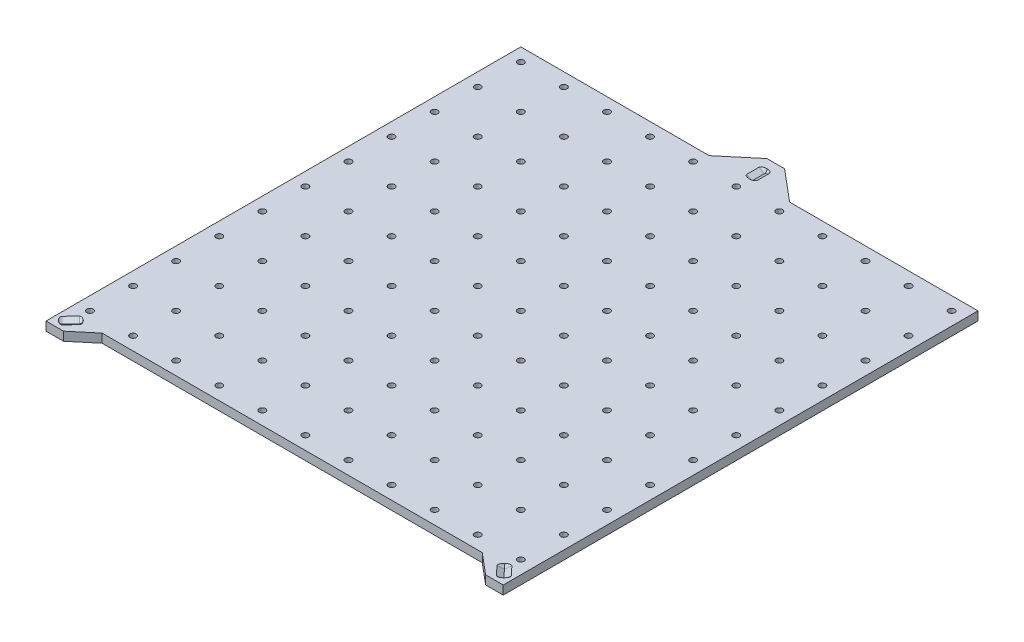
SolidWorks part; units mm, degrees
material "1060 Alloy"
ref_plane "Front Plane" through (0, 0, 0) normal (0, 0, 1) x (1, 0, 0)
ref_plane "Top Plane" through (0, 0, 0) normal (0, 1, 0) x (1, 0, 0)
ref_plane "Right Plane" through (0, 0, 0) normal (1, 0, 0) x (0, 0, -1)
sketch "Sketch1" plane through (0, 0, 0) normal (0, 1, 0) x (1, 0, 0)
  line L0 (-260, -260) -> (-260, -280)
  line L1 (260, 260) -> (45.7526, 260)
  line L2 (260, 260) -> (260, -260)
  line L3 (216.1649, -260) -> (-216.1649, -260)
  line L4 (-260, 260) -> (-260, -260)
  line L5 (260, 260) -> (-260, -260) construction
  line L6 (260, -260) -> (-260, 260) construction
  line L7 (-260, -280) -> (-240, -280)
  line L8 (-240, -280) -> (-216.1649, -260)
  line L9 (260, -260) -> (260, -280)
  line L10 (260, -280) -> (240, -280)
  line L11 (240, -280) -> (216.1649, -260)
  line L12 (0, 270) -> (0, 314.3126) construction
  line L13 (-45.7526, 260) -> (-10, 290)
  line L14 (-10, 290) -> (10, 290)
  line L15 (10, 290) -> (45.7526, 260)
  line L16 (-45.7526, 260) -> (-260, 260)
  line L17 (0, 0) -> (0, 290) construction
  point P0 (0, 0)
  dimension "D1" = 520
  dimension "D2" = 520
  dimension "D3" = 20
  dimension "D4" = 20
  dimension "D5" = 40
  dimension "D6" = 520
  dimension "D7" = 20
  dimension "D8" = 40
  dimension "D9" = 520
  dimension "D10" = 30
  dimension "D11" = 20
  dimension "D12" = 10
  dimension "D13" = 40
  dimension "D14" = 40
extrude "Boss-Extrude1" add sketch "Sketch1" along normal blind 10
ref_axis "Axis1" through (0, 10.5, 0) along (0, -1, 0)
ref_plane "Plane2" through (0, 0, 0) normal (-0.7328, 0, -0.6805) x (-0.6805, 0, 0.7328)
ref_plane "Plane3" through (-260, 0, 280) normal (0.6805, 0, -0.7328) x (0, -1, 0)
ref_plane "Plane4" through (-253.1955, 0, 272.6721) normal (0.6805, 0, -0.7328) x (0, -1, 0)
sketch "Sketch5" plane through (-253.1955, 0, 272.6721) normal (0.6805, 0, -0.7328) x (0, -1, 0)
  line L0 (-10, -13.609) -> (-10, 143.3901) construction
  line L2 (-10, 6) -> (-10, -6)
  line L3 (-10, 6) -> (-6.5359, 0)
  line L4 (-6.5359, 0) -> (-10, -6)
  line L5 (-10.5, 0) -> (0.5, 0) construction
  dimension "D1" = 30
  dimension "D2" = 30
  dimension "D3" = 12
extrude "Cut-Extrude1" cut sketch "Sketch5" along normal blind 20
fillet "Fillet1" radius 3 4 edges at (-241.7848, 8.2679, 255.9748) (-237.3881, 8.2679, 260.0575) (-250.9971, 8.2679, 274.7134) (-255.3939, 8.2679, 270.6307)
ref_plane "Plane5" through (-246.391, 0, 265.3441) normal (0.6805, 0, -0.7328) x (0, -1, 0)
mirror "Mirror1" about plane through (0, 0, 0) normal (1, 0, 0) of "Fillet1", "Cut-Extrude1"
ref_plane "Plane6" through (0, 0, -280) normal (0, 0, -1) x (-1, 0, 0)
sketch "Sketch6" plane through (0, 0, -280) normal (0, 0, -1) x (-1, 0, 0)
  line L0 (-10, 10) -> (10, 10) construction
  line L1 (0, 10.5) -> (0, -0.5) construction
  line L2 (-6, 10) -> (6, 10)
  line L3 (6, 10) -> (0, 6.5359)
  line L4 (0, 6.5359) -> (-6, 10)
  dimension "D1" = 12
  dimension "D2" = 30
  dimension "D3" = 30
extrude "Cut-Extrude2" cut sketch "Sketch6" against normal blind 20
fillet "Fillet2" radius 3 4 edges at (3, 8.2679, -260) (-3, 8.2679, -260) (3, 8.2679, -280) (-3, 8.2679, -280)
ref_axis "Axis2" through (-246.391, -0.5, 265.3441) along (0, 1, 0)
ref_plane "Plane7" through (251.1541, 0, 270.4737) normal (0.6805, 0, 0.7328) x (0.7328, 0, -0.6805)
ref_plane "Plane8" through (246.391, 0, 265.3441) normal (0.6805, 0, 0.7328) x (0.7328, 0, -0.6805)
ref_plane "Plane9" through (0, 0, 0) normal (-0.7328, 0, 0.6805) x (0.6805, 0, 0.7328)
ref_axis "Axis3" through (246.391, 10.1732, 265.3441) along (0, -1, 0)
ref_plane "Plane10" through (0, 0, -263) normal (0, 0, 1) x (1, 0, 0)
ref_plane "Plane11" through (0, 0, -270) normal (0, 0, 1) x (1, 0, 0)
ref_axis "Axis4" through (0, 10.5, -270) along (0, -1, 0)
sketch "Sketch7" plane through (0, 0, 0) normal (0, -1, 0) x (1, 0, 0)
  line L0 (247.7871, 264.0477) -> (244.9948, 266.6406) construction
  circle A0 centre (-246.391, 265.3441) radius 6.25
  circle A1 centre (246.391, 265.3441) radius 6.25
  circle A2 centre (0, -270) radius 6.25
  dimension "D1" = 12.5
  dimension "D2" = 12.5
  dimension "D3" = 12.5
extrude "Cut-Extrude3" cut sketch "Sketch7" against normal blind 5.5
sketch "Sketch8" plane through (0, 10, 0) normal (0, 1, 0) x (1, 0, 0)
  line L1 (245, 245) -> (-245, 245) construction
  line L2 (245, 245) -> (245, -245) construction
  line L3 (245, -245) -> (-245, -245) construction
  line L4 (-245, 245) -> (-245, -245) construction
  line L5 (245, 245) -> (-245, -245) construction
  line L6 (245, -245) -> (-245, 245) construction
  circle A0 centre (-245, -245) radius 3.6
  circle A1 centre (-196, -245) radius 3.6
  circle A2 centre (-147, -245) radius 3.6
  circle A3 centre (-98, -245) radius 3.6
  circle A4 centre (-49, -245) radius 3.6
  circle A5 centre (0, -245) radius 3.6
  circle A6 centre (49, -245) radius 3.6
  circle A7 centre (98, -245) radius 3.6
  circle A8 centre (147, -245) radius 3.6
  circle A9 centre (196, -245) radius 3.6
  circle A10 centre (245, -245) radius 3.6
  circle A11 centre (-196, -196) radius 3.6
  circle A12 centre (-147, -196) radius 3.6
  circle A13 centre (-98, -196) radius 3.6
  circle A14 centre (-49, -196) radius 3.6
  circle A15 centre (0, -196) radius 3.6
  circle A16 centre (49, -196) radius 3.6
  circle A17 centre (98, -196) radius 3.6
  circle A18 centre (147, -196) radius 3.6
  circle A19 centre (196, -196) radius 3.6
  circle A20 centre (245, -196) radius 3.6
  circle A21 centre (-196, -147) radius 3.6
  circle A22 centre (-147, -147) radius 3.6
  circle A23 centre (-98, -147) radius 3.6
  circle A24 centre (-49, -147) radius 3.6
  circle A25 centre (0, -147) radius 3.6
  circle A26 centre (49, -147) radius 3.6
  circle A27 centre (98, -147) radius 3.6
  circle A28 centre (147, -147) radius 3.6
  circle A29 centre (196, -147) radius 3.6
  circle A30 centre (245, -147) radius 3.6
  circle A31 centre (-196, -98) radius 3.6
  circle A32 centre (-147, -98) radius 3.6
  circle A33 centre (-98, -98) radius 3.6
  circle A34 centre (-49, -98) radius 3.6
  circle A35 centre (0, -98) radius 3.6
  circle A36 centre (49, -98) radius 3.6
  circle A37 centre (98, -98) radius 3.6
  circle A38 centre (147, -98) radius 3.6
  circle A39 centre (196, -98) radius 3.6
  circle A40 centre (245, -98) radius 3.6
  circle A41 centre (-196, -49) radius 3.6
  circle A42 centre (-147, -49) radius 3.6
  circle A43 centre (-98, -49) radius 3.6
  circle A44 centre (-49, -49) radius 3.6
  circle A45 centre (0, -49) radius 3.6
  circle A46 centre (49, -49) radius 3.6
  circle A47 centre (98, -49) radius 3.6
  circle A48 centre (147, -49) radius 3.6
  circle A49 centre (196, -49) radius 3.6
  circle A50 centre (245, -49) radius 3.6
  circle A51 centre (-196, 0) radius 3.6
  circle A52 centre (-147, 0) radius 3.6
  circle A53 centre (-98, 0) radius 3.6
  circle A54 centre (-49, 0) radius 3.6
  circle A55 centre (0, 0) radius 3.6
  circle A56 centre (49, 0) radius 3.6
  circle A57 centre (98, 0) radius 3.6
  circle A58 centre (147, 0) radius 3.6
  circle A59 centre (196, 0) radius 3.6
  circle A60 centre (245, 0) radius 3.6
  circle A61 centre (-196, 49) radius 3.6
  circle A62 centre (-147, 49) radius 3.6
  circle A63 centre (-98, 49) radius 3.6
  circle A64 centre (-49, 49) radius 3.6
  circle A65 centre (0, 49) radius 3.6
  circle A66 centre (49, 49) radius 3.6
  circle A67 centre (98, 49) radius 3.6
  circle A68 centre (147, 49) radius 3.6
  circle A69 centre (196, 49) radius 3.6
  circle A70 centre (245, 49) radius 3.6
  circle A71 centre (-196, 98) radius 3.6
  circle A72 centre (-147, 98) radius 3.6
  circle A73 centre (-98, 98) radius 3.6
  circle A74 centre (-49, 98) radius 3.6
  circle A75 centre (0, 98) radius 3.6
  circle A76 centre (49, 98) radius 3.6
  circle A77 centre (98, 98) radius 3.6
  circle A78 centre (147, 98) radius 3.6
  circle A79 centre (196, 98) radius 3.6
  circle A80 centre (245, 98) radius 3.6
  circle A81 centre (-196, 147) radius 3.6
  circle A82 centre (-147, 147) radius 3.6
  circle A83 centre (-98, 147) radius 3.6
  circle A84 centre (-49, 147) radius 3.6
  circle A85 centre (0, 147) radius 3.6
  circle A86 centre (49, 147) radius 3.6
  circle A87 centre (98, 147) radius 3.6
  circle A88 centre (147, 147) radius 3.6
  circle A89 centre (196, 147) radius 3.6
  circle A90 centre (245, 147) radius 3.6
  circle A91 centre (-196, 196) radius 3.6
  circle A92 centre (-147, 196) radius 3.6
  circle A93 centre (-98, 196) radius 3.6
  circle A94 centre (-49, 196) radius 3.6
  circle A95 centre (0, 196) radius 3.6
  circle A96 centre (49, 196) radius 3.6
  circle A97 centre (98, 196) radius 3.6
  circle A98 centre (147, 196) radius 3.6
  circle A99 centre (196, 196) radius 3.6
  circle A100 centre (245, 196) radius 3.6
  circle A101 centre (-196, 245) radius 3.6
  circle A102 centre (-147, 245) radius 3.6
  circle A103 centre (-98, 245) radius 3.6
  circle A104 centre (-49, 245) radius 3.6
  circle A105 centre (0, 245) radius 3.6
  circle A106 centre (49, 245) radius 3.6
  circle A107 centre (98, 245) radius 3.6
  circle A108 centre (147, 245) radius 3.6
  circle A109 centre (196, 245) radius 3.6
  circle A110 centre (245, 245) radius 3.6
  circle A111 centre (-245, -196) radius 3.6
  circle A112 centre (-245, -147) radius 3.6
  circle A113 centre (-245, -98) radius 3.6
  circle A114 centre (-245, -49) radius 3.6
  circle A115 centre (-245, 0) radius 3.6
  circle A116 centre (-245, 49) radius 3.6
  circle A117 centre (-245, 98) radius 3.6
  circle A118 centre (-245, 147) radius 3.6
  circle A119 centre (-245, 196) radius 3.6
  circle A120 centre (-245, 245) radius 3.6
  point P0 (0, 0)
  dimension "D3" = 7.2
  dimension "D1" = 490
  dimension "D2" = 490
  dimension "D4" = 11
  dimension "D5" = 11
extrude "Cut-Extrude4" cut sketch "Sketch8" against normal offset from surface (8.5 mm away) 1.5 up to face at (-246.391, 0, 259.0941)
